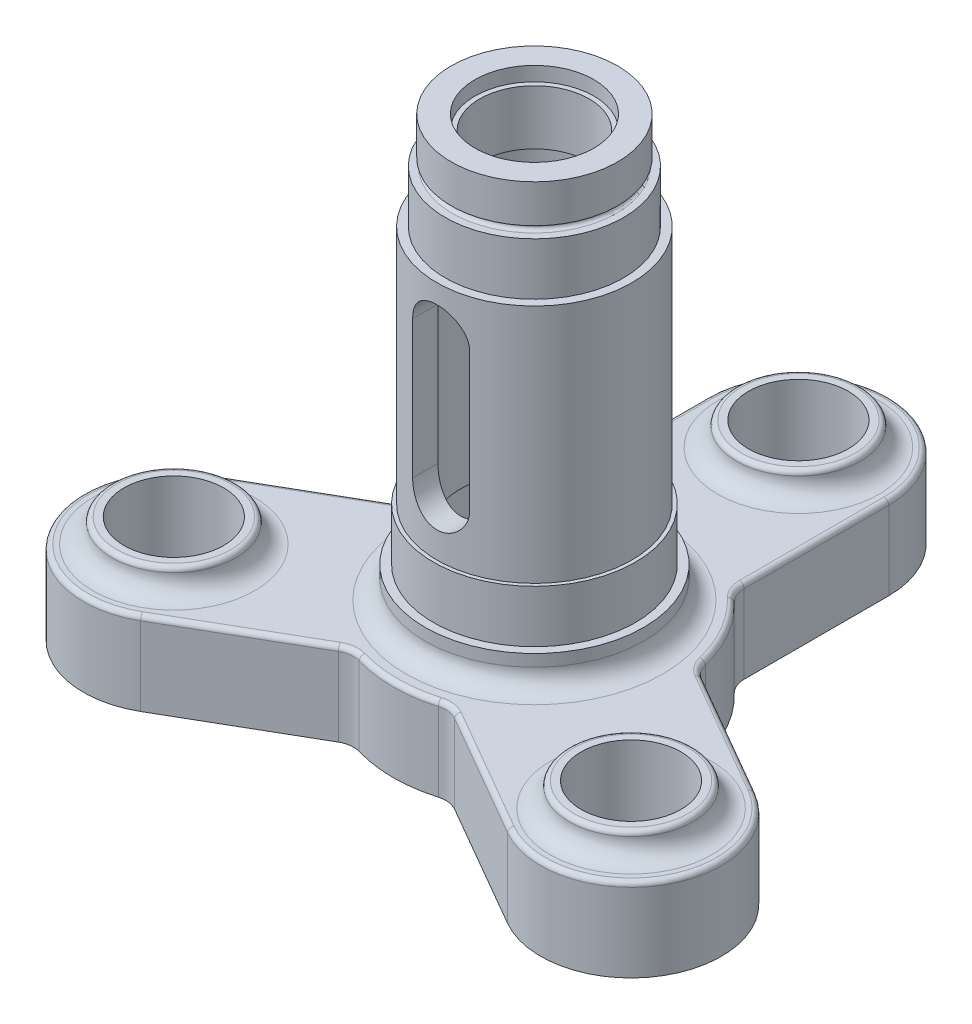
SolidWorks part; units mm, degrees
note: The reader was unsure of these and kept them because the rebuilt part matched: shared geometry of "Schizzo1<5>".
ref_plane "Piano frontale" through (0, 0, 0) normal (0, 0, 1) x (1, 0, 0)
ref_plane "Piano superiore" through (0, 0, 0) normal (0, 1, 0) x (1, 0, 0)
ref_plane "Piano destro" through (0, 0, 0) normal (1, 0, 0) x (0, 0, -1)
sketch "Schizzo1" plane through (0, 0, 0) normal (0, 1, 0) x (1, 0, 0)
  line L0 (0, 139.765) -> (0, -131.5564) construction
  line L1 (-131.1205, 0) -> (135.6974, 0) construction
  line L2 (0, 0) -> (96.1288, -55.5) construction
  line L3 (0, 0) -> (-96.1288, -55.5) construction
  line L4 (96.1288, -55.5) -> (39.5629, -22.8417) construction
  line L5 (77.1288, -88.409) -> (20.5629, -55.7506)
  line L6 (115.1288, -22.591) -> (58.5629, 10.0673)
  line L7 (-96.1288, -55.5) -> (-39.5629, -22.8417) construction
  line L8 (-115.1288, -22.591) -> (-58.5629, 10.0673)
  line L9 (-77.1288, -88.409) -> (-20.5629, -55.7506)
  line L10 (0, 111) -> (0, 45.6833) construction
  line L11 (38, 111) -> (38, 45.6833)
  line L12 (-38, 111) -> (-38, 45.6833)
  circle A0 centre (0, 0) radius 111 construction
  circle A4 centre (0, 111) radius 26
  circle A5 centre (0, 111) radius 21
  circle A21 centre (96.1288, -55.5) radius 26
  arc A22 (38, 111) -> (-38, 111) centre (0, 111) ccw
  arc A24 (77.1288, -88.409) -> (115.1288, -22.591) centre (96.1288, -55.5) ccw
  circle A26 centre (-96.1288, -55.5) radius 21
  circle A27 centre (-96.1288, -55.5) radius 26
  arc A28 (-115.1288, -22.591) -> (-77.1288, -88.409) centre (-96.1288, -55.5) ccw
  arc A30 (-38, 45.6833) -> (-58.5629, 10.0673) centre (0, 0) ccw
  arc A31 (-20.5629, -55.7506) -> (20.5629, -55.7506) centre (0, 0) ccw
  arc A32 (58.5629, 10.0673) -> (38, 45.6833) centre (0, 0) ccw
  circle A33 centre (96.1288, -55.5) radius 21 [skipped]
  circle A34 centre (96.1288, -55.5) radius 21
  point P7 (0, 78.3417)
  point P18 (0, 0)
  point P21 (67.8459, -39.1708)
  point P25 (0, 0)
  point P31 (-67.8459, -39.1708)
  point P38 (0, 0)
  point P39 (0, 0)
  point P43 (0, 0)
  dimension "D1" = 222
  dimension "D5" = 3
  dimension "D6" = 52
  dimension "D7" = 42
  dimension "D4" = 76
  dimension "D8" = 38
  dimension "D9" = 42
  dimension "D2" = 120
  dimension "D3" = 120
extrude "Estrusione-Estrusione3" add sketch "Schizzo1" along normal blind 45 contours A27 A26 | A21 A34 | A4 A5
extrude "Estrusione-Estrusione4" add sketch "Schizzo1<5>" along normal blind 35 contours L6 A32 L11 A22 L12 A30 L8 A28 L9 A31 L5 A24 A4 A21 A27
sketch "Schizzo1<5>" plane through (0, 0, 0) normal (0, 1, 0) x (1, 0, 0) same geometry as "Schizzo1"
fillet "Raccordo2" radius 10 6 edges at (-58.5629, 17.5, -10.0673) (-38, 17.5, -45.6833) (38, 17.5, -45.6833) (58.5629, 17.5, -10.0673) (20.5629, 17.5, 55.7506) (-20.5629, 17.5, 55.7506)
sketch "Schizzo3" plane through (0, 0, 0) normal (1, 0, 0) x (0, 0, -1)
  line L0 (46, 48) -> (46, 35)
  line L1 (46, 48) -> (42.5, 48)
  line L2 (42.5, 48) -> (42.5, 70)
  line L3 (41, 70) -> (41, 171)
  line L4 (0, 0) -> (0, 262.6504) construction
  line L5 (41, 171) -> (37.5, 171)
  line L6 (37.5, 171) -> (37.5, 193)
  line L7 (37.5, 193) -> (33, 193)
  line L8 (33, 193) -> (33, 196)
  line L9 (33, 196) -> (35, 196)
  line L10 (35, 196) -> (35, 212)
  line L11 (35, 212) -> (0, 212) construction
  line L13 (42.5, 48) -> (0, 48) construction
  line L14 (41, 70) -> (0, 70) construction
  line L15 (37.5, 171) -> (0, 171) construction
  line L16 (33, 193) -> (0, 193) construction
  line L17 (33, 196) -> (0, 196) construction
  line L18 (42.5, 70) -> (41, 70)
  line L19 (50.1538, 35) -> (42.9293, 35) construction
  line L21 (-93.5, 0) -> (-22.591, 0) construction
  dimension "D2" = 22
  dimension "D3" = 123
  dimension "D4" = 145
  dimension "D5" = 70
  dimension "D6" = 66
  dimension "D7" = 3
  dimension "D8" = 164
  dimension "D9" = 75
  dimension "D10" = 85
  dimension "D11" = 82
  dimension "D12" = 92
  dimension "D13" = 212
revolve "Rivoluzione-Sottile1" add sketch "Schizzo3" angle 360 about L4
cosmetic thread "Filettatura cosmetica1" parameters "D1"=5, "D2"=57.425
ref_plane "Piano1" through (0, 0, 41) normal (0, 0, 1) x (1, 0, 0)
sketch "Schizzo4" plane through (0, 0, 41) normal (0, 0, 1) x (1, 0, 0)
  line L0 (0, 151) -> (0, 93) construction
  line L1 (12, 151) -> (12, 93)
  line L2 (-12, 151) -> (-12, 93)
  line L3 (41, 171) -> (-41, 171) construction
  arc A0 (12, 151) -> (-12, 151) centre (0, 151) ccw
  arc A1 (-12, 93) -> (12, 93) centre (0, 93) ccw
  point P3 (0, 122)
  dimension "D3" = 12
  dimension "D1" = 20
  dimension "D2" = 58
extrude "Taglio-Estrusione1" cut sketch "Schizzo4" against normal through all
fillet "Raccordo3" radius 8 4 edges at (0, 35, -46) (96.1288, 35, 81.5) (-96.1288, 35, 81.5) (0, 35, -85)
fillet "Raccordo4" radius 2 21 edges at (50.7816, 35, 73.1974) (20.6309, 35, 56.718) (0, 35, 59.4219) (-20.6309, 35, 56.718) (-50.7816, 35, 73.1974) (-129.0378, 35, 74.5) (-88.7816, 35, 7.3795) (-59.4346, 35, -10.4921) (-51.4609, 35, -29.711) (-38.8037, 35, -46.2259) (-38, 35, -80.5769) (0, 35, -149) (38, 35, -80.5769) (38.8037, 35, -46.2259) (51.4609, 35, -29.711) (59.4346, 35, -10.4921) (88.7816, 35, 7.3795) (96.1288, 45, 81.5) (129.0378, 35, 74.5) (0, 45, -85) (-96.1288, 45, 81.5)
fillet "Raccordo5" radius 1.5 2 edges at (0, 193, -33) (0, 196, -33)
